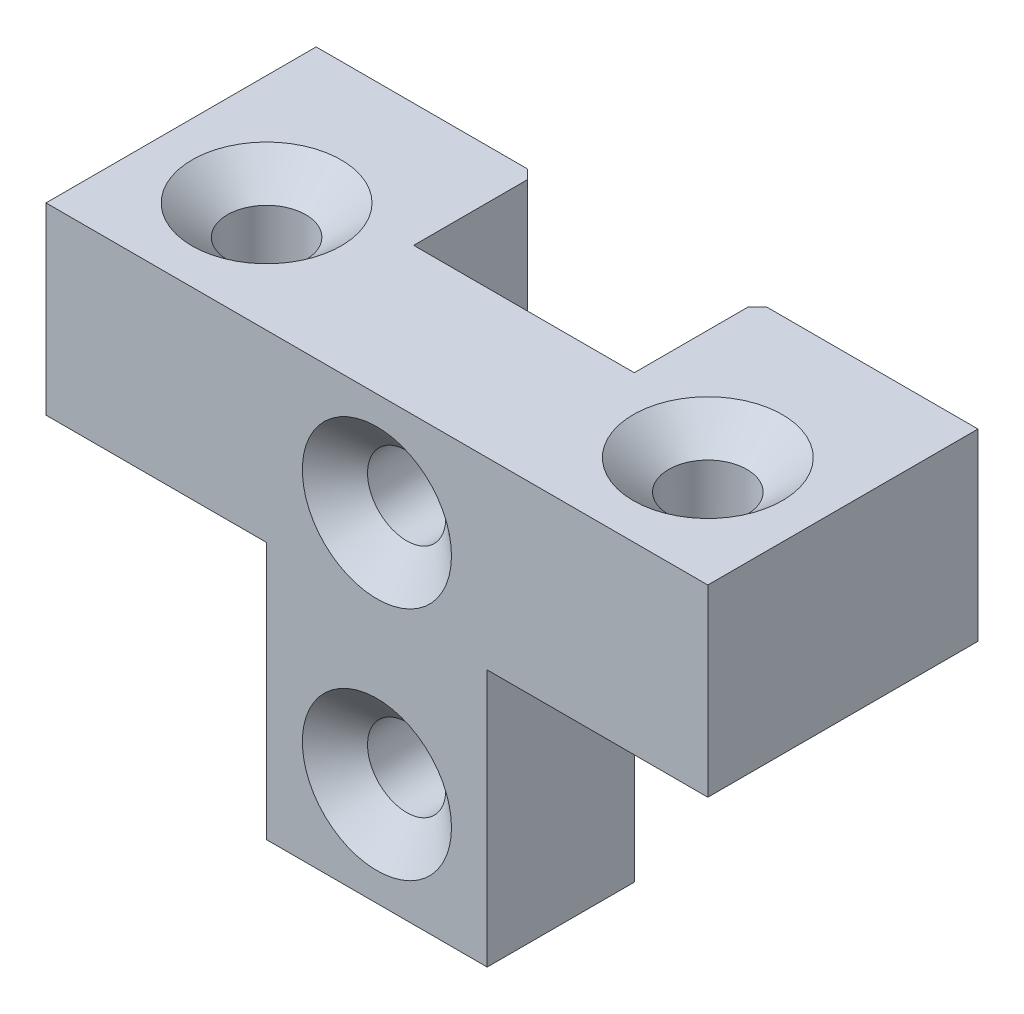
SolidWorks part; units mm, degrees
ref_plane "Front" through (0, 0, 0) normal (0, 0, 1) x (1, 0, 0)
ref_plane "Top" through (0, 0, 0) normal (0, 1, 0) x (1, 0, 0)
ref_plane "Right" through (0, 0, 0) normal (1, 0, 0) x (0, 0, -1)
sketch "Sketch1" plane through (0, 0, 0) normal (0, 0, 1) x (1, 0, 0)
  line L0 (0, 0) -> (22.2463, 0) construction
  line L1 (-28.575, 19.05) -> (28.575, 19.05)
  line L2 (19.05, 29.2913) -> (19.05, -10.8361) construction
  line L3 (9.525, 3.175) -> (19.05, 3.175)
  line L4 (28.575, 19.05) -> (28.575, 3.175)
  line L5 (19.05, 3.175) -> (28.575, 3.175)
  line L6 (0, 19.05) -> (0, -19.05) construction
  line L7 (-9.525, -19.05) -> (9.525, -19.05)
  line L8 (9.525, 3.175) -> (9.525, -19.05)
  line L9 (-9.525, 3.175) -> (-9.525, -19.05)
  line L10 (-9.525, 3.175) -> (-19.05, 3.175)
  line L11 (-19.05, 3.175) -> (-28.575, 3.175)
  line L12 (-28.575, 19.05) -> (-28.575, 3.175)
  dimension "D1" = 9.525
  dimension "D2" = 38.1
  dimension "D3" = 3.175
  dimension "D4" = 19.05
extrude "Boss-Extrude1" add sketch "Sketch1" against normal blind 12.7
hole_wizard "CSK for 1/4 Flat Head Machine Screw (100)1" positions "Sketch2" profile "Sketch3" countersink size "1/4" standard "ANSI Inch" end condition through all
sketch "Sketch2" plane through (0, 0, 0) normal (0, 0, 1) x (1, 0, 0)
  line L0 (0, 10.16) -> (0, -10.16) construction
  point P0 (0, 10.16)
  point P2 (0, -10.16)
  point P7 (0, 0)
  dimension "D1" = 20.32
sketch "Sketch3" plane through (0, 10.16, 0) normal (1, 0, 0) x (0, -1, 0)
  line L0 (0, 0) -> (0, 12.7)
  line L1 (0, 12.7) -> (3.3782, 12.7)
  line L2 (3.3782, 12.7) -> (3.3782, 2.5682)
  line L3 (3.3782, 2.5682) -> (6.4389, 0)
  line L5 (6.4389, 0) -> (0, 0)
  line L6 (-3.3782, 2.5682) -> (-6.4389, 0) construction
  line L11 (0, -6.35) -> (0, 107.95) construction
  dimension "Thru Hole Dia." = 6.7564
  dimension "Thru Hole Depth" = 12.7
  dimension "Near C'Sink Dia." = 12.8778
  dimension "Near C'Sink Angle" = 100
sketch "Sketch7" plane through (0, 19.05, 0) normal (0, 1, 0) x (1, 0, 0)
  line L0 (-28.575, 12.7) -> (-9.525, 12.7) construction
  line L1 (9.525, 12.7) -> (28.575, 12.7) construction
  line L2 (-28.575, 12.7) -> (-9.525, 12.7) construction
  line L3 (9.525, 12.7) -> (28.575, 12.7) construction
  line L4 (-9.525, 12.7) -> (-9.525, 11.1125)
  line L5 (-9.525, 11.1125) -> (9.525, 11.1125)
  line L6 (9.525, 11.1125) -> (9.525, 12.7)
  line L7 (9.525, 12.7) -> (-9.525, 12.7)
  line L8 (28.575, 0) -> (-28.575, 0) construction
  dimension "D1" = 11.1125
extrude "Cut-Extrude1" [suppressed] cut sketch "Sketch7" against normal through all
sketch "Sketch6" plane through (0, 0, -12.7) normal (0, 0, 1) x (1, 0, 0)
  line L0 (-9.525, 3.175) -> (-9.525, 19.05)
  line L1 (28.575, 19.05) -> (-28.575, 19.05) construction
  line L2 (9.525, 3.175) -> (9.525, 19.05)
  line L4 (-28.575, 3.175) -> (-9.525, 3.175) construction
  line L5 (28.575, 3.175) -> (28.575, 19.05) construction
  line L6 (9.525, 3.175) -> (28.575, 3.175) construction
  line L7 (9.525, 19.05) -> (28.575, 19.05)
  line L8 (28.575, 3.175) -> (28.575, 19.05)
  line L9 (9.525, 3.175) -> (28.575, 3.175)
  line L10 (-28.575, 3.175) -> (-28.575, 19.05)
  line L11 (-28.575, 3.175) -> (-9.525, 3.175)
  line L12 (-9.525, 19.05) -> (-28.575, 19.05)
extrude "Boss-Extrude2" add sketch "Sketch6" against normal blind 10.6299
hole_wizard "CSK for 1/4 Flat Head Machine Screw (100)2" positions "Sketch4" profile "Sketch5" countersink size "1/4" standard "ANSI Inch" end condition through all
sketch "Sketch4" plane through (0, 19.05, 0) normal (0, 1, 0) x (1, 0, 0)
  line L0 (-19.05, 9.525) -> (19.05, 9.525) construction
  line L5 (0, 9.525) -> (0, 0) construction
  line L6 (28.575, 0) -> (-28.575, 0) construction
  point P0 (-19.05, 9.525)
  point P2 (19.05, 9.525)
  dimension "D1" = 38.1
  dimension "D2" = 9.525
sketch "Sketch5" plane through (-19.05, 19.05, -9.525) normal (1, 0, 0) x (0, 0, 1)
  line L0 (0, 0) -> (0, 38.1)
  line L1 (0, 38.1) -> (3.3782, 38.1)
  line L2 (3.3782, 38.1) -> (3.3782, 2.5682)
  line L3 (3.3782, 2.5682) -> (6.4389, 0)
  line L5 (6.4389, 0) -> (0, 0)
  line L6 (-3.3782, 2.5682) -> (-6.4389, 0) construction
  line L11 (0, -6.35) -> (0, 107.95) construction
  dimension "Thru Hole Dia." = 6.7564
  dimension "Thru Hole Depth" = 38.1
  dimension "Near C'Sink Dia." = 12.8778
  dimension "Near C'Sink Angle" = 100
chamfer "Chamfer1" distance 0.7937 angle 45 2 edges at (-9.525, 11.1125, -23.3299) (9.525, 11.1125, -23.3299)
